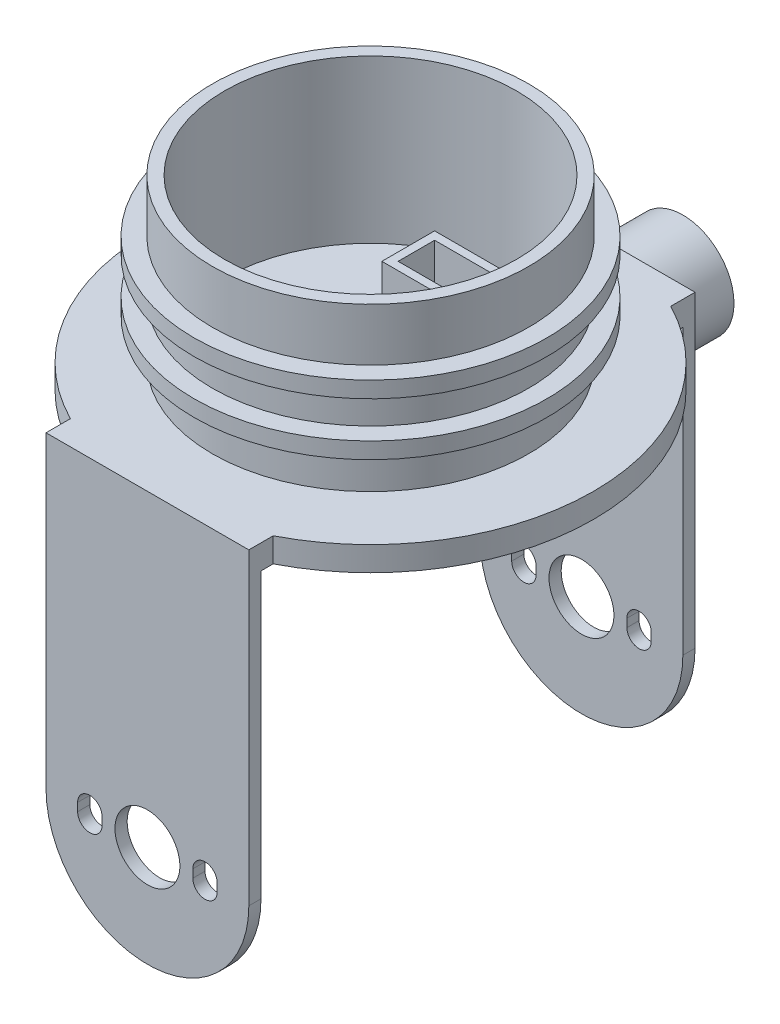
SolidWorks part; units mm, degrees
ref_plane "前基準面" through (0, 0, 0) normal (0, 0, 1) x (1, 0, 0)
ref_plane "上基準面" through (0, 0, 0) normal (0, 1, 0) x (1, 0, 0)
ref_plane "右基準面" through (0, 0, 0) normal (1, 0, 0) x (0, 0, -1)
sketch "草圖1" plane through (0, 0, 0) normal (0, 1, 0) x (1, 0, 0)
  circle A0 centre (0, 0) radius 19.5
  circle A1 centre (0, 0) radius 18
  dimension "D1" = 39
  dimension "D2" = 36
extrude "填料-伸長1" add sketch "草圖1" along normal blind 20
sketch "草圖3" plane through (0, 0, 0) normal (0, -1, 0) x (1, 0, 0)
  circle A0 centre (0, 0) radius 27.5
  dimension "D1" = 55
extrude "填料-伸長2" add sketch "草圖3" along normal blind 3
ref_plane "平面2" through (0, -3, 0) normal (0, -1, 0) x (-1, 0, 0)
ref_plane "平面5" through (0, 0, 0) normal (0, 1, 0) x (1, 0, 0)
ref_plane "平面6" through (0, 7, 0) normal (0, -1, 0) x (-1, 0, 0)
sketch "草圖25" plane through (0, 7, 0) normal (0, -1, 0) x (-1, 0, 0)
  circle A0 centre (0, 0) radius 21.75
  circle A1 centre (0, 0) radius 19.5
  dimension "D1" = 43.5
extrude "填料-伸長12" add sketch "草圖25" along normal blind 2
ref_plane "平面10" through (0, 10.5, 0) normal (0, -1, 0) x (-1, 0, 0)
sketch "草圖26" plane through (0, 10.5, 0) normal (0, -1, 0) x (-1, 0, 0)
  circle A0 centre (0, 0) radius 21.75
  circle A1 centre (0, 0) radius 19.5
extrude "填料-伸長13" add sketch "草圖26" against normal blind 2 from offset 1 offset against normal yes
sketch "草圖27" plane through (0, -3, 0) normal (0, -1, 0) x (1, 0, 0)
  line L0 (0, 0) -> (-12.5, 0)
  line L1 (46.0389, 0) -> (-46.0389, 0) construction
  line L2 (-12.5, 0) -> (-12.5, 27.5)
  line L3 (-12.5, 27.5) -> (12.5, 27.5)
  line L4 (12.5, 27.5) -> (12.5, 0)
  line L5 (12.5, 0) -> (-12.5, 0)
  line L6 (-12.5, 0) -> (-12.5, -26)
  line L7 (-12.5, -26) -> (12.5, -26)
  line L8 (12.5, -26) -> (12.5, 0)
  circle M6 centre (0, 0) radius 27.5
  dimension "D1" = 26
  dimension "D2" = 27.5
extrude "填料-伸長14" add sketch "草圖27" against normal blind 3 contours L8 L5 L0 L6 L7 M6 | L5 L4 L3 L2 L0 M6 | L6 L7 M6 | L7 L8 M6 | L4 L3 M6 | L3 L2 M6 region at (0, -3, -12.9033) region at (0, -3, 13.2755) region at (-9.4102, -3, 26.6076) region at (-11.3596, -3, -25.514) region at (9.4102, -3, 26.6076) region at (11.3596, -3, -25.514)
sketch "草圖28" plane through (0, 0, -26) normal (0, 0, -1) x (-1, 0, 0)
  line L0 (12.5, -3) -> (12.5, -38)
  line L1 (12.5, -38) -> (-12.5, -38)
  line L2 (-12.5, -38) -> (-12.5, 0)
  line L3 (-12.5, 0) -> (12.5, 0)
  line L4 (12.5, 0) -> (12.5, -3) construction
  line L5 (12.5, 0) -> (12.5, -3)
  line L6 (-7.1, -37.5) -> (-7.1, -38.5) construction
  line L7 (-5.6, -37.5) -> (-5.6, -38.5)
  line L8 (-8.6, -37.5) -> (-8.6, -38.5)
  line L9 (12.5, -3) -> (-12.5, -3)
  line L10 (7.1, -37.5) -> (7.1, -38.5) construction
  line L11 (8.6, -37.5) -> (8.6, -38.5)
  line L12 (5.6, -37.5) -> (5.6, -38.5)
  arc A0 (12.5, -38) -> (-12.5, -38) centre (0, -38) cw
  circle A1 centre (0, -38) radius 4
  arc A2 (-5.6, -37.5) -> (-8.6, -37.5) centre (-7.1, -37.5) ccw
  arc A3 (-8.6, -38.5) -> (-5.6, -38.5) centre (-7.1, -38.5) ccw
  arc A4 (8.6, -37.5) -> (5.6, -37.5) centre (7.1, -37.5) ccw
  arc A5 (5.6, -38.5) -> (8.6, -38.5) centre (7.1, -38.5) ccw
  point P14 (-7.1, -38)
  point P19 (-7.1, -36)
  point P20 (-7.1, -40)
  point P26 (7.1, -38)
  point P31 (7.1, -36)
  point P32 (7.1, -40)
  line M17 (8.9582, 0) -> (8.9582, -3)
  line M18 (8.9582, -3) -> (12.5, -3)
  line M19 (12.5, -3) -> (12.5, 0)
  line M20 (12.5, 0) -> (8.9582, 0)
  dimension "D1" = 8
  dimension "D2" = 4
  dimension "D3" = 3
  dimension "D4" = 5.6
  dimension "D5" = 4
  dimension "D6" = 3
  dimension "D7" = 5.6
  dimension "D8" = 35
extrude "填料-伸長17" add sketch "草圖28" along normal blind 1.5 contours A4 L11 L1 L0 L9 L2 L8 A2 L7 A1 L12 M18 | L9 L3 L2 M17 | M20 M17 M18 M19 | A5 L12 L1 A1 L7 A3 L8 A0 L11 region at (-10.7291, -1.5, -26) region at (0, -19.8277, -26) region at (0, -43.9487, -26) region at (1.7709, -1.5, -26)
extrude "填料-伸長25" add sketch "草圖28<25>" against normal blind 53.5 contours A4 L11 L1 L0 L9 L2 L8 A2 L7 A1 L12 M18 | A5 L12 L1 A1 L7 A3 L8 A0 L11 region at (0, -19.8277, -26) region at (0, -43.9487, -26)
sketch "草圖28<25>" plane through (0, 0, -26) normal (0, 0, -1) x (-1, 0, 0) same geometry as "草圖28"
sketch "草圖38" plane through (0, 0, -27.5) normal (0, 0, -1) x (-1, 0, 0)
  line L0 (-28.6, -3) -> (28.6, -3) construction
  line L1 (0, -9.8) -> (-1, -14.4947) construction
  line L2 (-1, -14.4947) -> (-1.3125, -15.9618) construction
  line L3 (0, 0) -> (0, -50.5) construction
  line L4 (0, -9.8) -> (1, -14.4947) construction
  line L5 (1, -14.4947) -> (1.3125, -15.9618) construction
  line L6 (-1, -14.4947) -> (-1.3125, -15.9618)
  line L7 (1, -14.4947) -> (1.3125, -15.9618)
  arc A0 (-12.5, -38) -> (12.5, -38) centre (0, -38) ccw construction
  circle A2 centre (0, -9.8) radius 4.8
  circle A3 centre (0, -9.8) radius 6.3
  arc A4 (1, -14.4947) -> (-1, -14.4947) centre (0, -9.8) ccw
  dimension "D1" = 6.8
  dimension "D2" = 9.6
  dimension "D3" = 12.6
  dimension "D4" = 2
  dimension "D5" = 1
extrude "除料-伸長15" cut sketch "草圖28<27>" against normal blind 52 contours A5 L12 L1 A1 L7 A3 L8 A0 L11 | A4 L11 L1 L0 L9 L2 L8 A2 L7 A1 L12 M18 region at (0, -19.8277, -26) region at (0, -43.9487, -26)
sketch "草圖28<27>" plane through (0, 0, -26) normal (0, 0, -1) x (-1, 0, 0) same geometry as "草圖28"
extrude "填料-伸長24" add sketch "草圖38<4>" along normal blind 11 contours L7 A3 L6 A2 region at (1.3296, -15.1913, -27.5)
sketch "草圖38<4>" plane through (0, 0, -27.5) normal (0, 0, -1) x (-1, 0, 0) same geometry as "草圖38"
extrude "除料-伸長10" cut sketch "草圖38" against normal blind 1.5 contours A2 L6 region at (0, -9.8, -27.5)
sketch "草圖34" plane through (0, 0, 0) normal (0, 1, 0) x (1, 0, 0)
  line L0 (0, 0) -> (-17.3838, 0) construction
  line L1 (-17.3838, 0) -> (19.1481, 0) construction
  line L2 (0, 0) -> (0, -21.2728) construction
  line L3 (0, -21.2728) -> (0, 19.1859) construction
  line L4 (5.1, 13) -> (-5.1, 13) construction
  line L5 (-4.1, 12) -> (4.1, 12)
  line L6 (-4.1, 12) -> (-4.1, 7.5)
  line L7 (-4.1, 7.5) -> (4.1, 7.5)
  line L8 (4.1, 12) -> (4.1, 7.5)
  line L10 (5.1, 6.5) -> (-5.1, 6.5)
  line L11 (5.1, 6.5) -> (5.1, 13)
  line L12 (5.1, 13) -> (-5.1, 13)
  line L13 (-5.1, 6.5) -> (-5.1, 13)
  point P13 (0, 13)
  dimension "D1" = 8.2
  dimension "D2" = 4.5
  dimension "D3" = 1
  dimension "D4" = 12
  dimension "D5" = 1
  dimension "D6" = 1
  dimension "D7" = 1
extrude "填料-伸長22" add sketch "草圖34" along normal blind 5
sketch "草圖37" plane through (0, 0, 0) normal (0, 1, 0) x (1, 0, 0)
  line L2 (-4.1, 12) -> (4.1, 12)
  line L3 (-4.1, 12) -> (-4.1, 7.5)
  line L4 (-4.1, 7.5) -> (4.1, 7.5)
  line L5 (4.1, 12) -> (4.1, 7.5)
extrude "除料-伸長9" cut sketch "草圖37" against normal blind 5
extrude "填料-伸長26" add sketch "草圖38<12>" along normal blind 8 contours L6 A3 L7 A2 region at (0, -15.3429, -27.5)
sketch "草圖38<12>" plane through (0, 0, -27.5) normal (0, 0, -1) x (-1, 0, 0) same geometry as "草圖38"
